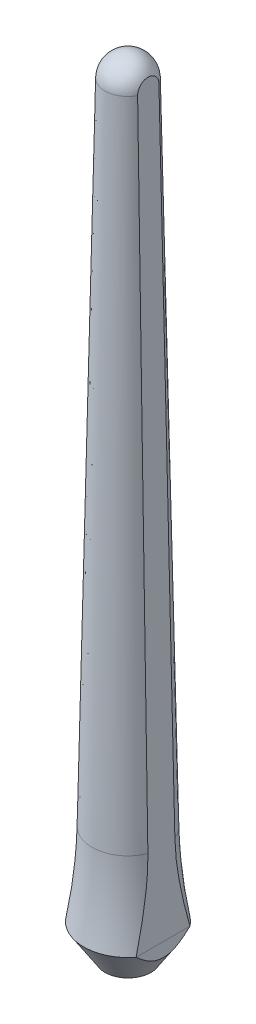
SolidWorks part; units mm, degrees
ref_plane "Front Plane" through (0, 0, 0) normal (0, 0, 1) x (1, 0, 0)
ref_plane "Top Plane" through (0, 0, 0) normal (0, 1, 0) x (1, 0, 0)
ref_plane "Right Plane" through (0, 0, 0) normal (1, 0, 0) x (0, 0, -1)
sketch "Sketch1" plane through (0, 0, 0) normal (0, 0, 1) x (1, 0, 0)
  line L0 (0, 0) -> (0, 120)
  line L1 (3.5, 116.57) -> (5.5, 17.562)
  line L2 (6.75, 5) -> (3.5, 0)
  line L3 (3.5, 0) -> (0, 0)
  line L4 (0, 0) -> (0, -29.0188) construction
  arc A0 (0, 120) -> (3.5, 116.57) centre (0, 116.4993) cw
  arc A1 (5.5, 17.562) -> (6.75, 5) centre (85.4837, 19.1777) ccw
  dimension "D2" = 7
  dimension "D3" = 80
  dimension "D1" = 120
  dimension "D4" = 13.5
  dimension "D5" = 7
  dimension "D6" = 11
  dimension "D7" = 5
revolve "Revolve1" add sketch "Sketch1" angle 360 about L4
sketch "Sketch2" plane through (0, 0, 0) normal (0, -1, 0) x (1, 0, 0)
  circle A0 centre (0, 0) radius 2.2
  dimension "D1" = 4.4
extrude "Cut-Extrude1" cut sketch "Sketch2" against normal blind 14
ref_plane "Plane1" through (0, 5, 0) normal (0, -1, 0) x (-1, 0, 0)
sketch "Sketch3" plane through (0, 0, 0) normal (0, 0, 1) x (1, 0, 0)
  line L0 (2.8286, 130) -> (5.8587, -20)
  line L1 (5.8587, -20) -> (20, -20)
  line L2 (20, -20) -> (20, 130)
  line L3 (20, 130) -> (2.8286, 130)
  line L4 (3.5, 116.57) -> (5.5, 17.562) construction
  line L5 (0, 0) -> (0, -29.0188) construction
  dimension "D1" = 0.4
  dimension "D2" = 150
  dimension "D3" = 20
  dimension "D4" = 20
extrude "Cut-Extrude2" cut sketch "Sketch3" against normal mid plane 20
pattern_circular "CirPattern1" [suppressed] count 3 over 360 about axis through (0, 0, 0) along (0, -1, 0) of bodies 105 106
chamfer "Chamfer1" distance 0.2 angle 75 1 edges at (0, 0, -2.2) first distance on face at (0, 0, -2.2)
split "Split1" trim tools "Plane1" bodies to split 105 resulting bodies 109 110
chamfer "Chamfer2" distance 0.5 angle 45 1 edges at (0, 14, -2.2)
